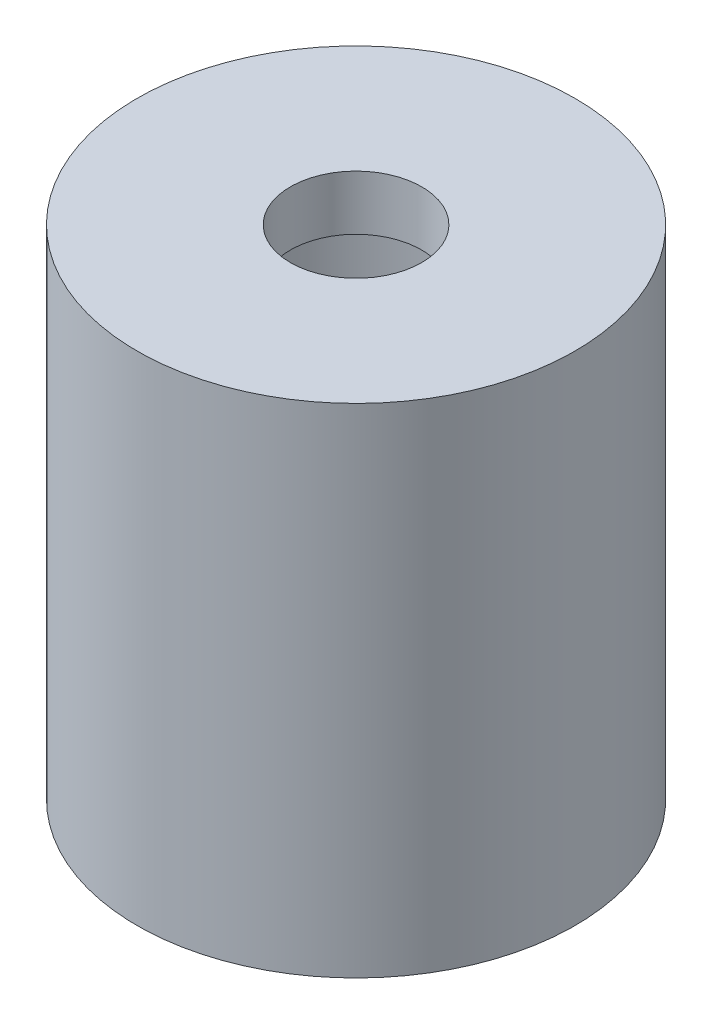
SolidWorks part; units mm, degrees
material "6061-T6 (SS)"
ref_plane "Piano frontale" through (0, 0, 0) normal (0, 0, 1) x (1, 0, 0)
ref_plane "Piano superiore" through (0, 0, 0) normal (0, 1, 0) x (1, 0, 0)
ref_plane "Piano destro" through (0, 0, 0) normal (1, 0, 0) x (0, 0, -1)
sketch "Schizzo1" plane through (0, 0, 0) normal (0, 0, 1) x (1, 0, 0)
  line L0 (0, 0) -> (0, 23.6846) construction
  line L1 (-14, 0) -> (-14, 30)
  line L2 (-14, 30) -> (0, 30)
  line L3 (0, 30) -> (0, 35)
  line L4 (0, 35) -> (-20, 35)
  line L5 (-20, 35) -> (-20, 0)
  line L6 (-20, 0) -> (-14, 0)
  line L7 (-20, 0) -> (-20, -10.4579)
  line L8 (-20, -10.4579) -> (-18, -10.4579)
  line L9 (-18, 0) -> (-18, -12) construction
  line L10 (-18, -10.4579) -> (-18, 0)
  line L11 (-18, 0) -> (-18, -12) construction
  dimension "D1" = 28
  dimension "D2" = 40
  dimension "D3" = 5
  dimension "D4" = 30
revolve "Rivoluzione1" add sketch "Schizzo1" angle 360 about L0 region at (-14.5, 21.25, 0) region at (-19, -5.229, 0)
sketch "Schizzo2" plane through (0, 35, 0) normal (0, 1, 0) x (1, 0, 0)
  circle A0 centre (0, 0) radius 6
  dimension "D1" = 12
extrude "Taglio-Estrusione1" cut sketch "Schizzo2" against normal blind 11
